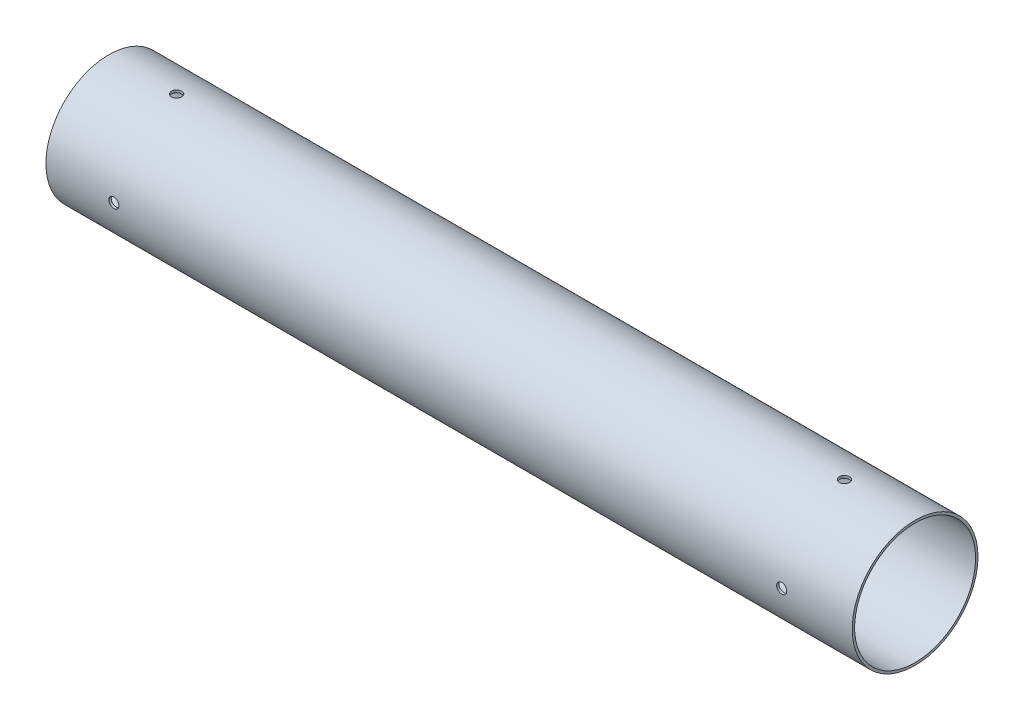
SolidWorks part; units mm, degrees
ref_plane "Front Plane" through (0, 0, 0) normal (1, 0, 0) x (0, 1, 0)
ref_plane "Top Plane" through (0, 0, 0) normal (0, 0, 1) x (0, 1, 0)
ref_plane "Right Plane" through (0, 0, 0) normal (0, 1, 0) x (-1, 0, 0)
sketch "Sketch1" plane through (0, 0, 0) normal (1, 0, 0) x (0, 1, 0)
  circle A0 centre (0, 0) radius 39.624
  circle A1 centre (0, 0) radius 38.1
  dimension "D1" = 79.248
  dimension "D2" = 76.2
extrude "Boss-Extrude1" add sketch "Sketch1" along normal blind 508
sketch "Sketch2" plane through (0, 0, 0) normal (0, 1, 0) x (-1, 0, 0)
  circle A0 centre (-42.8244, 0) radius 3.175
  dimension "D1" = 6.35
  dimension "D2" = 42.8244
extrude "Cut-Extrude1" cut sketch "Sketch2" along normal through all
pattern_circular "CirPattern1" count 4 over 360 about axis through (508, 0, 0) along (-1, 0, 0) of "Cut-Extrude1" reverse direction yes
sketch "Sketch3" plane through (0, 0, 0) normal (0, 1, 0) x (-1, 0, 0)
  line L0 (-508, 39.624) -> (-508, -39.624) construction
  circle A0 centre (-463.55, 0) radius 3.175
  point P5 (0, 0)
  dimension "D2" = 6.35
  dimension "D1" = 44.45
extrude "Cut-Extrude2" cut sketch "Sketch3" along normal through all
pattern_circular "CirPattern2" count 4 over 360 about axis through (508, 0, 0) along (-1, 0, 0) of "Cut-Extrude2"
